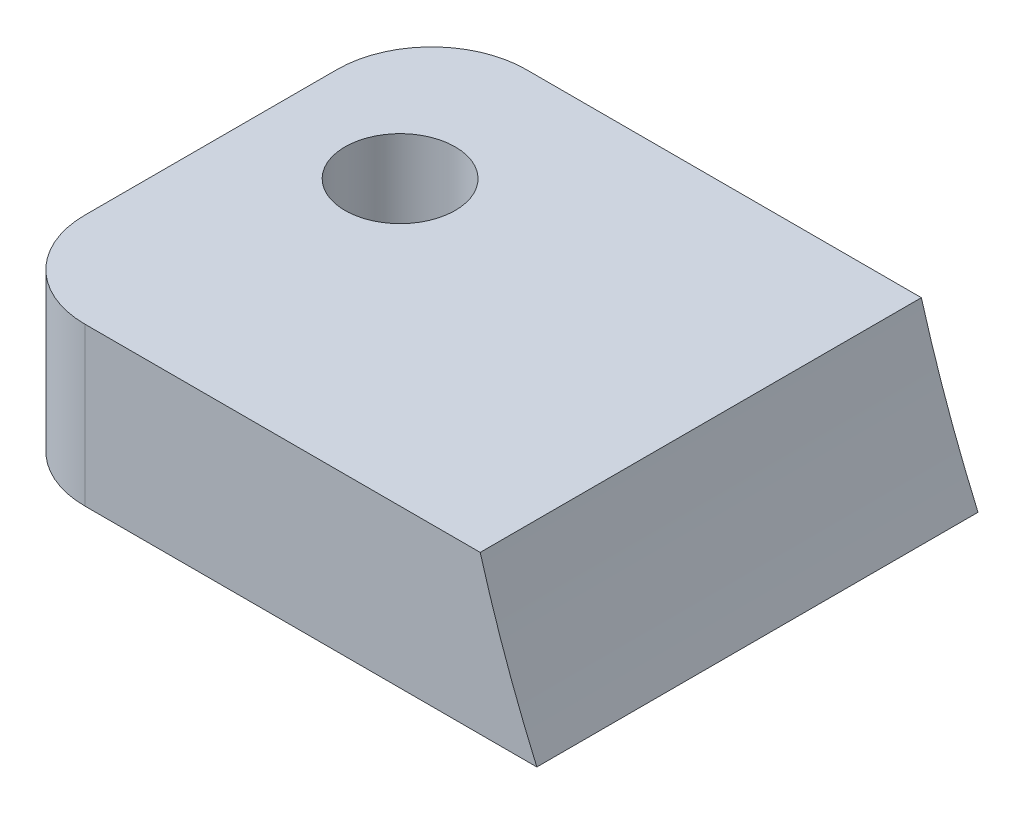
SolidWorks part; units mm, degrees
material "Acrylic (Medium-high impact)"
ref_plane "Front Plane" through (0, 0, 0) normal (0, 0, 1) x (1, 0, 0)
ref_plane "Top Plane" through (0, 0, 0) normal (0, 1, 0) x (1, 0, 0)
ref_plane "Right Plane" through (0, 0, 0) normal (1, 0, 0) x (0, 0, -1)
ref_axis "Axis1" through (0, 0, -0.7) along (0, 0, 1)
sketch "Sketch1" plane through (0, 0, 0) normal (0, 0, 1) x (1, 0, 0)
  circle A0 centre (0, 0) radius 38
  circle A1 centre (0, 0) radius 40
  dimension "D1" = 76
  dimension "D2" = 2
extrude "Boss-Extrude1" add sketch "Sketch1" along normal blind 200
ref_plane "Plane1" through (0, 0, 180) normal (0, 0, 1) x (1, 0, 0)
sketch "Sketch2" plane through (0, 0, 180) normal (0, 0, 1) x (1, 0, 0)
  circle A0 centre (0, 0) radius 40 construction
  circle A1 centre (0, 0) radius 40
extrude "Boss-Extrude2" add sketch "Sketch2" along normal blind 2
sketch "Sketch3" plane through (0, 0, 0) normal (0, 0, -1) x (-1, 0, 0)
  line L0 (-24, -32) -> (-72, -32)
  line L1 (-72, -32) -> (-72, -30)
  line L2 (-72, -30) -> (-26.4575, -30)
  line L3 (-24, 32) -> (-72, 32)
  line L4 (-72, 30) -> (-26.4575, 30)
  line L5 (-72, 32) -> (-72, 30)
  line L6 (-40, -15.2942) -> (-40, 13.2229) construction
  line L8 (0, 0) -> (-59.0266, 0) construction
  circle A1 centre (0, 0) radius 40 construction
  arc A2 (-24, 32) -> (-26.4575, 30) centre (0, 0) ccw
  arc A3 (-26.4575, -30) -> (-24, -32) centre (0, 0) ccw
  dimension "D1" = 60
  dimension "D2" = 2
  dimension "D3" = 32
extrude "Boss-Extrude3" add sketch "Sketch3" against normal blind 107
sketch "Sketch4" plane through (0, 0, 107) normal (0, 0, 1) x (1, 0, 0)
  line L2 (72, -32) -> (24, -32) construction
  line L3 (24, 32) -> (72, 32) construction
  line L4 (72, -32) -> (24, -32)
  line L5 (24, 32) -> (72, 32)
  line L6 (72, -32) -> (72, 32)
  circle A0 centre (0, 0) radius 40 construction
  arc A2 (24, -32) -> (24, 32) centre (0, 0) ccw
extrude "Boss-Extrude4" add sketch "Sketch4" along normal blind 2
sketch "Sketch5" plane through (0, 32, 0) normal (0, 1, 0) x (1, 0, 0)
  circle A5 centre (43.5, -102.5) radius 1.75 construction
  circle A6 centre (43.5, -102.5) radius 1.75
  circle A7 centre (43.5, -3.5) radius 1.75 construction
  circle A8 centre (43.5, -3.5) radius 1.75
  circle A9 centre (68.5, -78) radius 1.75 construction
  circle A10 centre (68.5, -78) radius 1.75
extrude "Cut-Extrude1" cut sketch "Sketch5" against normal through all
ref_plane "Plane2" through (0, 0, 0) normal (-0.7071, 0.7071, 0) x (0, 0, 1)
sketch "Sketch6" plane through (0, 0, 0) normal (-0.7071, 0.7071, 0) x (0, 0, 1)
  line L0 (200, -40) -> (200, 40) construction
  line L1 (200, -40) -> (200, 40) construction
  circle A0 centre (187, 0) radius 4
  dimension "D1" = 8
  dimension "D2" = 13
extrude "Cut-Extrude2" cut sketch "Sketch6" against normal up to next and the other way up to next
pattern_circular "CirPattern1" count 2 every 90 about axis through (0, 0, -0.7) along (0, 0, 1) of "Cut-Extrude2"
ref_plane "Plane3" through (-54, 0, 0) normal (1, 0, 0) x (0, 0, -1)
sketch "Sketch7" plane through (-54, 0, 0) normal (1, 0, 0) x (0, 0, -1)
  line L0 (0, 0) -> (-33.0452, 0) construction
  line L1 (-14, -11) -> (0, -11)
  line L2 (-14, -11) -> (-14, -16)
  line L3 (-14, -16) -> (0, -16)
  line L4 (0, -11) -> (0, -16)
  line L5 (0, -40) -> (0, 40) construction
  line L6 (0, 11) -> (0, 16)
  line L7 (-14, 16) -> (0, 16)
  line L8 (-14, 11) -> (-14, 16)
  line L9 (-14, 11) -> (0, 11)
  dimension "D1" = 5
  dimension "D2" = 14
  dimension "D3" = 22
extrude "Boss-Extrude5" add sketch "Sketch7" along normal up to surface (15.5422 mm away) up to face at (25.3934, 30.9059, 187.8976)
sketch "Sketch8" plane through (0, -16, 0) normal (0, -1, 0) x (1, 0, 0)
  line L0 (0, -0.7) -> (0, 14.7) construction
  line L7 (-36.6606, 0) -> (-54, 0) construction
  circle A0 centre (-50, 5) radius 1.75
  dimension "D3" = 3.5
  dimension "D1" = 50
  dimension "D2" = 5
extrude "Cut-Extrude3" cut sketch "Sketch8" against normal up to surface (32 mm away) up to face at (-45.3303, 16, 7)
fillet "Fillet1" radius 3 4 edges at (-54, 13.5, 0) (-54, -13.5, 0) (-54, -13.5, 14) (-54, 13.5, 14)
sketch "Sketch9" plane through (0, 11, 0) normal (0, -1, 0) x (1, 0, 0)
  circle A0 centre (-44, 7) radius 0.25
  circle A1 centre (-50, 5) radius 1.75 construction
  dimension "D1" = 6
  dimension "D2" = 2
  dimension "D3" = 0.5
extrude "Cut-Extrude4" cut sketch "Sketch9" against normal up to next
sketch "Sketch10" plane through (0, 0, 0) normal (0, 0, -1) x (-1, 0, 0)
  line L0 (-10, 38.7298) -> (-10, 36.6606)
  line L2 (10, 38.7298) -> (10, 36.6606)
  line L3 (-10, -36.6606) -> (-10, -38.7298)
  line L4 (10, -36.6606) -> (10, -38.7298)
  line L5 (-10, 36.6606) -> (10, 36.6606) construction
  line L6 (0, 36.6606) -> (0, 0) construction
  circle A0 centre (0, 0) radius 38 construction
  arc A1 (36.6606, 16) -> (-24, 32) centre (0, 0) ccw construction
  arc A2 (-10, -36.6606) -> (10, -36.6606) centre (0, 0) ccw
  arc A3 (36.6606, 16) -> (-10, 38.7298) centre (0, 0) ccw
  arc A4 (10, 36.6606) -> (-10, 36.6606) centre (0, 0) ccw
  arc A5 (-24, -32) -> (36.6606, -16) centre (0, 0) ccw construction
  arc A6 (-10, -38.7298) -> (36.6606, -16) centre (0, 0) ccw
  arc M9 (36.6606, 16) -> (-24, 32) centre (0, 0) ccw
  arc M17 (-24, -32) -> (36.6606, -16) centre (0, 0) ccw
  circle M22 centre (0, 0) radius 38
  dimension "D1" = 20
extrude "Boss-Extrude6" add sketch "Sketch10" along normal blind 2 contours L4 L3 M22 M17 | L2 L0 M9 M22 region at (0, 38.5641, 0) region at (0, -38.5641, 0)
sketch "Sketch11" plane through (0, 0, 200) normal (0, 0, 1) x (1, 0, 0)
  arc A0 (-39.954, 1.9182) -> (9.219, -38.9231) centre (0, 0) ccw
  arc A1 (-0.3313, 39.9986) -> (-39.954, 1.9182) centre (-56.2112, 58.4877) ccw
  arc A2 (9.219, -38.9231) -> (9.219, 38.9231) centre (48.6167, 0) ccw
  arc A3 (9.219, 38.9231) -> (-0.3313, 39.9986) centre (0, 0) ccw
extrude "Cut-Extrude5" cut sketch "Sketch11" against normal up to next
